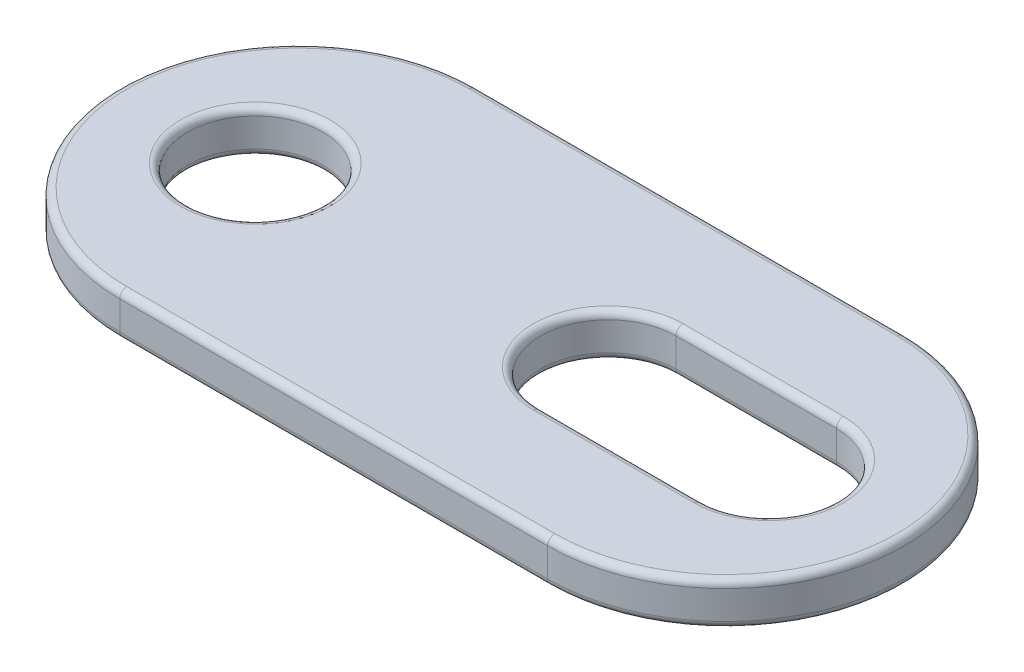
SolidWorks part; units mm, degrees
material "AISI 304"
ref_plane "Front" through (0, 0, 0) normal (0, 0, 1) x (1, 0, 0)
ref_plane "Top" through (0, 0, 0) normal (0, 1, 0) x (1, 0, 0)
ref_plane "Right" through (0, 0, 0) normal (1, 0, 0) x (0, 0, -1)
sketch "Sketch1" plane through (0, 0, 0) normal (0, 1, 0) x (1, 0, 0)
  line L1 (0, 0) -> (15.24, 0)
  line L2 (11.049, 8.763) -> (16.764, 8.763)
  line L3 (0, 12.7) -> (15.24, 12.7)
  line L5 (11.049, 3.937) -> (16.764, 3.937)
  arc A0 (0, 12.7) -> (0, 0) centre (0, 6.35) ccw
  arc A1 (15.24, 0) -> (15.24, 12.7) centre (15.24, 6.35) ccw
  circle A2 centre (-1.524, 6.35) radius 2.413
  arc A3 (11.049, 8.763) -> (11.049, 3.937) centre (11.049, 6.35) ccw
  arc A4 (16.764, 3.937) -> (16.764, 8.763) centre (16.764, 6.35) ccw
  dimension "D3" = 4.826
  dimension "D1" = 12.7
  dimension "D2" = 15.24
  dimension "D4" = 1.524
  dimension "D5" = 4.826
  dimension "D6" = 2.413
  dimension "D7" = 1.524
  dimension "D8" = 5.715
sheet metal parameters "Sheet-Metal1" thickness 1.524 parameters "D1"=3.81
base flange "Base-Flange1" sketch "Sketch1" thickness 1.524 reverse thickness direction yes parameters "D1"=3.81
fillet "Fillet2" radius 0.254 18 edges at (13.9065, 0, -8.763) (19.177, 0, -6.35) (13.9065, 0, -3.937) (8.636, 0, -6.35) (7.62, 0, 0) (21.59, 0, -6.35) (7.62, 0, -12.7) (-6.35, 0, -6.35) (-1.524, 0, -3.937) (19.177, 1.524, -6.35) (13.9065, 1.524, -8.763) (8.636, 1.524, -6.35) (13.9065, 1.524, -3.937) (7.62, 1.524, -12.7) (21.59, 1.524, -6.35) (7.62, 1.524, 0) (-6.35, 1.524, -6.35) (-1.524, 1.524, -3.937)
flat pattern "Flat-Pattern1" [suppressed]
sketch "Bend-Lines1" plane through (0, 0, 0) normal (0, 1, 0) x (-1, 0, 0)
